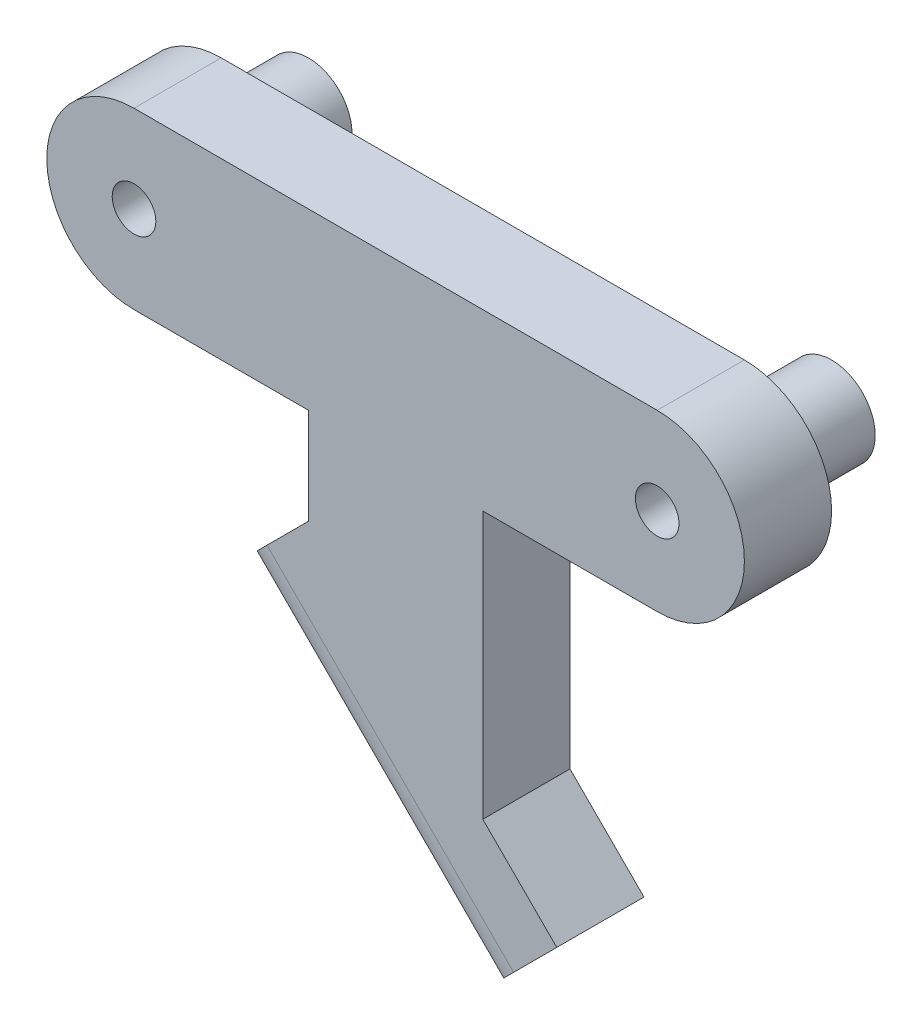
SolidWorks part; units mm, degrees
ref_plane "Piano frontale" through (0, 0, 0) normal (0, 0, 1) x (1, 0, 0)
ref_plane "Piano superiore" through (0, 0, 0) normal (0, 1, 0) x (1, 0, 0)
ref_plane "Piano destro" through (0, 0, 0) normal (1, 0, 0) x (0, 0, -1)
sketch "Schizzo1" plane through (0, 0, 0) normal (0, 0, 1) x (1, 0, 0)
  line L1 (-13.208, 5) -> (16.792, 5)
  line L2 (-13.208, -5) -> (-3.208, -5)
  line L3 (6.792, -28.7941) -> (6.792, -18.7941)
  line L4 (-3.208, -18.7941) -> (6.792, -28.7941)
  line L5 (6.792, -5) -> (16.792, -5)
  line L7 (-3.208, -5) -> (-3.208, -18.7941)
  line L9 (6.792, -5) -> (6.792, -18.7941)
  line L10 (6.792, 0) -> (16.792, 0) construction
  arc A0 (-13.208, 5) -> (-13.208, -5) centre (-13.208, 0) ccw
  arc A1 (16.792, -5) -> (16.792, 5) centre (16.792, 0) ccw
  point P3 (1.792, 0)
  dimension "D1" = 30
  dimension "D2" = 10
  dimension "D3" = 10
  dimension "D4" = 10
extrude "Estrusione-Estrusione3" add sketch "Schizzo1" along normal blind 5 contours L2 L7 L4 L3 L9 L5 A1 L1 A0
sketch "Schizzo3" plane through (0, 0, 0) normal (0, 0, -1) x (-1, 0, 0)
  line L6 (13.208, 5) -> (-16.792, 5)
  line L7 (-16.792, -5) -> (-6.792, -5)
  line L8 (-6.792, -5) -> (-6.792, -28.7941)
  line L9 (-6.792, -28.7941) -> (3.208, -18.7941)
  line L10 (3.208, -18.7941) -> (3.208, -5)
  line L11 (3.208, -5) -> (13.208, -5)
  line L12 (13.208, 5) -> (-16.792, 5) construction
  line L13 (-16.792, -5) -> (-6.792, -5) construction
  line L14 (-6.792, -5) -> (-6.792, -28.7941) construction
  line L15 (-6.792, -28.7941) -> (3.208, -18.7941) construction
  line L16 (3.208, -18.7941) -> (3.208, -5) construction
  line L17 (3.208, -5) -> (13.208, -5) construction
  circle A0 centre (-16.792, 0) radius 2.5
  circle A1 centre (13.208, 0) radius 2.5
  arc A2 (13.208, -5) -> (13.208, 5) centre (13.208, 0) ccw
  arc A3 (-16.792, 5) -> (-16.792, -5) centre (-16.792, 0) ccw
  arc A4 (13.208, -5) -> (13.208, 5) centre (13.208, 0) ccw construction
  arc A5 (-16.792, 5) -> (-16.792, -5) centre (-16.792, 0) ccw construction
  dimension "D1" = 0
extrude "Estrusione-Estrusione4" add sketch "Schizzo3" along normal blind 5
ref_plane "Piano1" through (17.7931, -17.7931, 0) normal (-0.7071, 0.7071, 0) x (0, 0, -1)
sketch "Schizzo7" plane through (17.7931, -17.7931, 0) normal (-0.7071, 0.7071, 0) x (0, 0, -1)
  line L0 (-5, 15.5578) -> (-5, -1.2671) construction
  line L1 (0, 15.5578) -> (-5, 15.5578)
  line L2 (0, 15.5578) -> (0, 9.5578)
  line L3 (0, 9.5578) -> (-5, 9.5578)
  line L4 (-5, 15.5578) -> (-5, 9.5578)
  dimension "D1" = 6
extrude "Estrusione-Estrusione5" add sketch "Schizzo7" along normal blind 20
sketch "Schizzo6" plane through (17.7931, -17.7931, 0) normal (-0.7071, 0.7071, 0) x (0, 0, -1)
  line L0 (0, -1.2671) -> (0, 9.5578) construction
  line L1 (-5, 15.5578) -> (0, 15.5578) construction
  circle A0 centre (-2.5, 12.5578) radius 1.65
  dimension "D1" = 3.3
  dimension "D2" = 2.5
  dimension "D3" = 3
extrude "Taglio-Estrusione1" cut sketch "Schizzo6" along normal up to surface (20 mm away) up to face at (-5.2791, -12.5809, 2.5)
fillet "Raccordo1" radius 2.5 2 edges at (-0.2791, -21.723, 0) (-0.2791, -21.723, 5)
sketch "Schizzo8" plane through (0, 0, -5) normal (0, 0, -1) x (-1, 0, 0)
  circle A0 centre (-16.792, 0) radius 1.25
  circle A1 centre (13.208, 0) radius 1.25
  dimension "D1" = 2.5
extrude "Taglio-Estrusione2" cut sketch "Schizzo8" against normal through all
